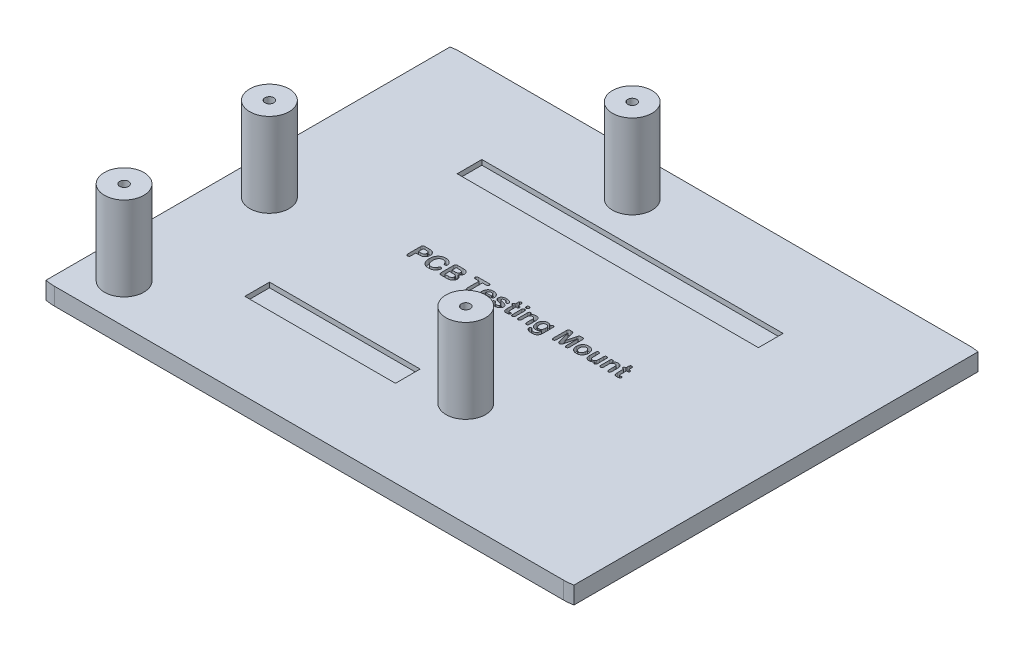
SolidWorks part; units mm, degrees
ref_plane "Front Plane" through (0, 0, 0) normal (0, 0, 1) x (1, 0, 0)
ref_plane "Top Plane" through (0, 0, 0) normal (0, 1, 0) x (1, 0, 0)
ref_plane "Right Plane" through (0, 0, 0) normal (1, 0, 0) x (0, 0, -1)
sketch "Sketch2" plane through (0, 0, 0) normal (0, 1, 0) x (1, 0, 0)
  line L0 (0, 0) -> (102, 0) construction
  line L1 (0, 0) -> (0, -77.2) construction
  line L2 (102, 0) -> (102, -77.2) construction
  line L3 (0, -77.2) -> (102, -77.2) construction
  line L4 (51, 0) -> (51, -77.2) construction
  line L5 (0, -38.6) -> (102, -38.6) construction
  line L6 (-2.5, 2.5) -> (104.5, 2.5)
  line L7 (-2.5, -79.7) -> (104.5, -79.7)
  line L8 (104.5, 2.5) -> (144.7372, -14.2911)
  line L9 (104.5, -79.7) -> (144.7372, -62.9089)
  line L10 (102, -38.6) -> (155.3, -38.6) construction
  line L11 (-2.5, -79.7) -> (-42.7372, -62.9089)
  line L12 (-2.5, 2.5) -> (-42.7372, -14.2911)
  line L13 (0, 0) -> (102, 0)
  line L14 (102, 0) -> (104.5, 0)
  line L15 (104.5, 0) -> (142.7026, -15.7437)
  line L16 (104.5, -77.2) -> (142.7026, -61.4563)
  line L17 (102, -77.2) -> (104.5, -77.2)
  line L18 (-2.5, -77.2) -> (-40.7026, -61.4563)
  line L19 (0, -77.2) -> (-2.5, -77.2)
  line L20 (-2.5, 0) -> (-40.7026, -15.7437)
  line L21 (0, 0) -> (-2.5, 0)
  line L22 (0, -77.2) -> (102, -77.2)
  line L23 (0, -76.7) -> (102, -76.7) construction
  line L24 (-2.5, -38.6) -> (-53.4807, -38.6) construction
  line L25 (-2.5, 0) -> (-2.5, -77.2) construction
  line L26 (104.5, 0) -> (104.5, -77.2) construction
  line L27 (0.5, 0) -> (0.5, -77.2) construction
  arc A0 (144.7372, -14.2911) -> (144.7372, -62.9089) centre (128.65, -38.6) cw
  arc A1 (-42.7372, -14.2911) -> (-42.7372, -62.9089) centre (-26.65, -38.6) ccw
  arc A2 (142.7026, -15.7437) -> (142.7026, -61.4563) centre (128.65, -38.6) cw
  arc A3 (-40.7026, -15.7437) -> (-40.7026, -61.4563) centre (-26.65, -38.6) ccw
  circle A4 centre (5.55, -71.7) radius 1.1
  circle A5 centre (5.6, -42.325) radius 1.1
  circle A6 centre (61.615, -58.575) radius 1.1
  circle A7 centre (42.614, -5.87) radius 1.1
  point P16 (157.8, -38.6)
  dimension "D3" = 2.5
  dimension "D10" = 2.5
  dimension "D11" = 5.05
  dimension "D12" = 5
  dimension "D13" = 34.375
  dimension "D15" = 18.125
  dimension "D17" = 42.114
  dimension "D1" = 77.2
  dimension "D2" = 102
  dimension "D4" = 2.5
  dimension "D5" = 2.5
  dimension "D6" = 2.5
  dimension "D7" = 0.5
  dimension "D8" = 2.5
  dimension "D9" = 53.3
  dimension "D14" = 5.1
  dimension "D16" = 61.115
  dimension "D18" = 70.83
  dimension "D19" = 0.5
extrude "MainExtrude" add sketch "Sketch2" along normal blind 33.1 contours A1 L11 L7 L9 A0 L8 L6 L12
extrude "MainCut" cut sketch "Sketch2<5>" along normal blind 50.8 contours L20 A3 L18 L19 L22 L17 L16 A2 L15 L14 L13 L21
sketch "Sketch2<5>" plane through (0, 0, 0) normal (0, 1, 0) x (1, 0, 0) same geometry as "Sketch2"
extrude "BassExtrude" add sketch "Sketch2<6>" against normal blind 3.5 contours L12 A1 L11 L7 L9 A0 L8 L6
sketch "Sketch2<6>" plane through (0, 0, 0) normal (0, 1, 0) x (1, 0, 0) same geometry as "Sketch2"
fillet "Fillet1" radius 10 4 edges at (104.5, 14.8, -2.5) (-2.5, 14.8, -2.5) (104.5, 14.8, 79.7) (-2.5, 14.8, 79.7)
sketch "Sketch6" plane through (0, 0, 0) normal (0, 1, 0) x (1, 0, 0)
  line L1 (-2.5, 0) -> (-2.5, -30)
  line L2 (-2.5, 0) -> (-2.5, -77.2) construction
  line L4 (-2.5, -77.2) -> (-2.5, -47.2)
  line L5 (-2.5, -47.2) -> (-52.065, -47.2) construction
  line L6 (-2.5, -30) -> (-52.065, -30) construction
  line L7 (-7.1001, -30) -> (-2.5, -30)
  line L8 (-2.5, -47.2) -> (-7.1001, -47.2)
  line L9 (-2.5, 0) -> (-40.7026, -15.7437)
  line L10 (-2.5, -77.2) -> (-40.7026, -61.4563)
  arc A2 (-40.7026, -15.7437) -> (-40.7026, -61.4563) centre (-26.65, -38.6) ccw
  arc A3 (-7.1001, -30) -> (-7.1001, -47.2) centre (-26.65, -38.6) ccw
  dimension "D1" = 30
  dimension "D2" = 30
extrude "Buzzer" add sketch "Sketch6" along normal blind 5
sketch "Sketch8" plane through (0, 0, 0) normal (0, 1, 0) x (1, 0, 0)
  text T0 "Buzzer" font "Arial Rounded MT Bold" height 3.5
  text T1 "PCB Testing Mount" font "Arial Rounded MT Bold" height 3.5
  text T2 "Speaker" font "Arial Rounded MT Bold" height 3.5
extrude "Text" cut sketch "Sketch8" against normal blind 1
sketch "Sketch9" plane through (0, 0, 0) normal (0, 1, 0) x (1, 0, 0)
  line L1 (104.5, -77.2) -> (104.5, -42.2)
  line L2 (104.5, 0) -> (104.5, -77.2) construction
  line L5 (104.5, -35) -> (109.5, -35)
  line L15 (104.5, -42.2) -> (109.5, -42.2)
  line L16 (109.5, -42.2) -> (109.5, -75.1394)
  line L17 (104.5, -77.2) -> (142.7026, -61.4563) construction
  line L18 (109.5, -75.1394) -> (104.5, -77.2)
  line L19 (109.5, -35) -> (123.6013, -7.8719)
  line L20 (104.5, 0) -> (142.7026, -15.7437) construction
  line L21 (104.5, -35) -> (119.4834, -6.1748)
  line L22 (142.7026, -15.7437) -> (104.5, 0) construction
  line L23 (119.4834, -6.1748) -> (123.6013, -7.8719)
  dimension "D3" = 5
  dimension "D2" = 35
  dimension "D4" = 5
sketch "Sketch10" plane through (0, 0, 0) normal (0, 1, 0) x (1, 0, 0)
  line L1 (20.5, -19.2) -> (81.5, -19.2)
  line L3 (20.5, -57.2) -> (51, -57.2)
  line L6 (20.5, -19.2) -> (20.5, -14.2)
  line L11 (20.5, -14.2) -> (81.5, -14.2)
  line L12 (81.5, -14.2) -> (81.5, -19.2)
  line L13 (20.5, -57.2) -> (20.5, -62.2)
  line L14 (20.5, -62.2) -> (51, -62.2)
  line L15 (51, -62.2) -> (51, -57.2)
  line L16 (51, 0) -> (51, -77.2) construction
  dimension "D1" = 0
  dimension "D2" = 5
  dimension "D3" = 38
  dimension "D4" = 61
  dimension "D5" = 5
  dimension "D6" = 30.5
extrude "Battery Cover Molds" cut sketch "Sketch10" against normal blind 1
sketch "Sketch11" plane through (0, 0, 0) normal (0, 1, 0) x (1, 0, 0)
  circle A0 centre (5.6, -42.325) radius 0.9
  circle A1 centre (5.6, -42.325) radius 4
  circle A2 centre (5.55, -71.7) radius 0.9
  circle A3 centre (5.55, -71.7) radius 4
  circle A4 centre (61.615, -58.575) radius 0.9
  circle A5 centre (61.615, -58.575) radius 4
  circle A6 centre (42.614, -5.87) radius 0.9
  circle A7 centre (42.614, -5.87) radius 4
extrude "PCB Offsets" add sketch "Sketch11" along normal blind 17
sketch "Sketch12" plane through (0, 0, -2.5) normal (0, 0, -1) x (-1, 0, 0)
  line L0 (-51, 0) -> (-51, 33.1) construction
  line L1 (2.5, 0) -> (-104.5, 0) construction
  line L2 (0.4972, 33.1) -> (-102.4972, 33.1) construction
  line L3 (-102.4972, 17) -> (0.4972, 17) construction
  line L4 (-102.4972, 33.1) -> (-102.4972, -3.5) construction
  line L5 (0.4972, -3.5) -> (0.4972, 33.1) construction
  line L8 (2.5, 0) -> (-104.5, 0) construction
  line L10 (-59, 17) -> (-49, 17)
  line L11 (-59, 17) -> (-59, 13)
  line L12 (-59, 13) -> (-49, 13)
  line L13 (-49, 17) -> (-49, 13)
  dimension "D1" = 17
  dimension "D2" = 4
  dimension "D3" = 10
  dimension "D4" = 2
extrude "USB" cut sketch "Sketch12" against normal up to next
fillet "Fillet2" radius 1.5 4 edges at (49, 13, -1.25) (59, 13, -1.25) (49, 17, -1.25) (59, 17, -1.25)
extrude "Cut-Extrude1" cut sketch "Sketch9" against normal blind 1
sketch "Sketch13" plane through (0, 33.1, 0) normal (0, 1, 0) x (1, 0, 0)
  line L1 (104.461, -79.5053) -> (158.2614, -79.5053)
  line L2 (104.461, -79.5053) -> (104.461, 2.3053)
  line L3 (104.461, 2.3053) -> (158.2614, 2.3053)
  line L4 (158.2614, -79.5053) -> (158.2614, 2.3053)
  line L5 (-2.461, -79.5053) -> (-56.4812, -79.5053)
  line L6 (-2.461, -79.5053) -> (-2.461, 2.3053)
  line L7 (-2.461, 2.3053) -> (-56.4812, 2.3053)
  line L8 (-56.4812, -79.5053) -> (-56.4812, 2.3053)
  arc A0 (102.4972, -79.7) -> (106.3483, -78.9287) centre (102.4972, -69.7) ccw construction
  arc A1 (-4.3483, -78.9287) -> (-0.4972, -79.7) centre (-0.4972, -69.7) ccw construction
extrude "Cut-Extrude2" cut sketch "Sketch13" against normal through all
sketch "Sketch14" plane through (0, 33.1, 0) normal (0, 1, 0) x (1, 0, 0)
  line L1 (104.461, 0) -> (-2.461, 0)
  line L2 (104.461, 0) -> (104.461, 2.5)
  line L3 (104.461, 2.5) -> (-2.461, 2.5)
  line L4 (-2.461, 0) -> (-2.461, 2.5)
  line L5 (104.461, -77.2) -> (-2.461, -77.2)
  line L6 (104.461, -77.2) -> (104.461, -79.7032)
  line L7 (104.461, -79.7032) -> (-2.461, -79.7032)
  line L8 (-2.461, -77.2) -> (-2.461, -79.7032)
extrude "Cut-Extrude3" cut sketch "Sketch14" against normal up to surface (33.1 mm away) up to face at (42.614, 0, 1.87)
